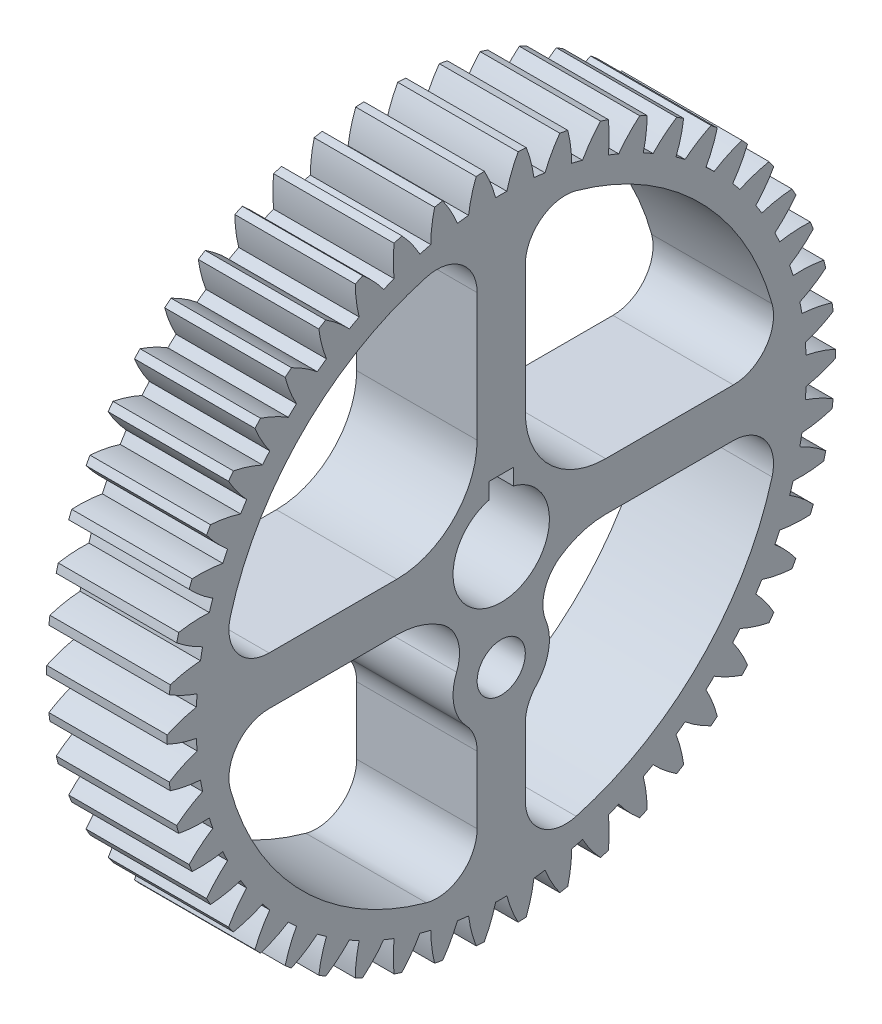
SolidWorks part; units mm, degrees
ref_plane "Plane1" through (0, 0, 0) normal (0, 0, 1) x (1, 0, 0)
ref_plane "Plane2" through (0, 0, 0) normal (0, 1, 0) x (1, 0, 0)
ref_plane "Plane3" through (0, 0, 0) normal (1, 0, 0) x (0, 0, -1)
other "Configuration Table"
sketch "HoldingSke" plane through (0, 0, 0) normal (0, 1, 0) x (1, 0, 0)
  line L0 (0, 0) -> (0.8035, -0.9576)
  line L1 (-15, 0) -> (100, 0) construction
  line L2 (0, 0) -> (-2.1039, 2.3779)
  line L3 (0, 0) -> (-11.863, 4.5341)
  line L4 (0, 0) -> (5.5511, 6.6156)
  line L5 (0, 0) -> (-46.8476, -17.4728)
  line L6 (0, 0) -> (-6.2172, -4.1948)
  line L7 (-2.1039, 2.3779) -> (8.6586, 51.2059)
  line L8 (-76.2, 54.61) -> (-76.1, 54.61)
  line L9 (-71.009, 38.7566) -> (-53.1078, 45.2721)
  line L10 (-76.2, 71.12) -> (104.1128, 71.12)
  line L11 (0, 0) -> (-7.5, 0)
  line L12 (-76.2, 101.6) -> (-76.17, 101.6)
  line L13 (24.9733, 27.94) -> (52.9518, 28.4284)
  line L14 (24.9733, 27.94) -> (24.9743, 27.94)
  line L15 (24.9733, 27.94) -> (100.4006, 29.5858)
  line L16 (-63.627, -0.8) -> (-12.827, -0.8)
  circle A0 centre (0, 0) radius 0.4
  circle A1 centre (0, 0) radius 18.999
  circle A2 centre (0, 0) radius 37.5
  circle A3 centre (0, 0) radius 0.4
  dimension "MHD" = 37.998
  dimension "Hub_dia" = 75
  dimension "Bore" = 0.8
  dimension "MBD" = 0.8
  dimension "Num_teeth" = 50
  dimension "Pitch" = 1.25
  dimension "Overall_len" = 50
  dimension "Show_teeth" = 50
  dimension "Thickness" = 7.5
  dimension "OAL" = 50.0001
  dimension "T_dim" = 0.1
  dimension "Ap" = 20
  dimension "H" = 19.05
  dimension "Pitch_radius" = 180.3128
  dimension "Width" = 7.5
  dimension "Backlash" = 0.03
  dimension "Addendum_fac" = 1
  dimension "Dedendum_fac" = 1.25
  dimension "Clearance_fac" = 0.25
  dimension "Dedendum_add" = 0.001
  dimension "Module" = 0.8
sketch "BasProSke" plane through (0, 0, 0) normal (0, 1, 0) x (1, 0, 0)
  line L0 (-10, 0) -> (60, 0) construction
  line L1 (0, 0) -> (0, 20.8)
  line L2 (0, 0) -> (7.5, 0)
  line L3 (7.5, 0) -> (7.5, 20.8)
  line L4 (7.5, 20.8) -> (0, 20.8)
  dimension "Thickness" = 7.5
  dimension "Diameter" = 41.6
revolve "Base-Revolve" add sketch "BasProSke" angle 360 about L0
sketch "TooCutSke" plane through (0, 0, 0) normal (1, 0, 0) x (0, 0, -1)
  line L1 (0, 0) -> (0, 107) construction
  line L2 (0, 0) -> (-0.6807, 19.9884) construction
  line L3 (0, 0) -> (-2.5106, 39.9045) construction
  line L4 (-0.6807, 19.9884) -> (-1.2553, 19.9523) construction
  arc A0 (0.3494, 18.9958) -> (-0.3494, 18.9958) centre (0, 0) ccw
  arc A1 (1.0655, 20.7981) -> (-1.0655, 20.7981) centre (0, 0) ccw
  circle A2 centre (0, 0) radius 20 construction
  circle A3 centre (0, 0) radius 18.7939 construction
  arc A4 (-0.3494, 18.9958) -> (-1.0655, 20.7981) centre (-8.0873, 16.9648) ccw
  arc A5 (1.0655, 20.7981) -> (0.3494, 18.9958) centre (8.0873, 16.9648) ccw
  dimension "Root_dia" = 37.998
  dimension "Overcut_dia" = 41.6508
  dimension "Pitch_dia" = 40
  dimension "Base_dia" = 37.5877
  dimension "Flank_rad" = 8
  dimension "Half_ang" = 3.6
  dimension "Half_CT" = 0.5757
extrude "ToothCut" cut sketch "TooCutSke" along normal through all
fillet "Breaks" [suppressed] radius 0.016 tangent propagation no
fillet "RootFillets" [suppressed] radius 0.201
pattern_circular "TeethCuts" count 50 every 7.2 about axis through (-10, 0, 0) along (1, 0, 0) of "ToothCut", "RootFillets", "Breaks"
sketch "HubNeaOneSke" plane through (0, 0, 0) normal (-1, 0, 0) x (0, 0, 1)
  circle A0 centre (0, 0) radius 18.999
  dimension "Diameter" = 37.998
extrude "HubNearOne" [suppressed] add sketch "HubNeaOneSke" along normal blind 42.5001
sketch "HubNeaBotSke" plane through (0, 0, 0) normal (-1, 0, 0) x (0, 0, 1)
  circle A0 centre (0, 0) radius 18.999
  dimension "Diameter" = 37.998
extrude "HubNearBoth" [suppressed] add sketch "HubNeaBotSke" along normal blind 21.25
ref_plane "FarPln" through (7.5, 0, 0) normal (1, 0, 0) x (0, 0, -1)
sketch "HubFarSke" plane through (7.5, 0, 0) normal (1, 0, 0) x (0, 0, -1)
  circle A0 centre (0, 0) radius 18.999
  dimension "Diameter" = 37.998
extrude "HubFar" [suppressed] add sketch "HubFarSke" along normal blind 21.25
sketch "BorSke" plane through (0, 0, 0) normal (1, 0, 0) x (0, 0, -1)
  circle A0 centre (0, 0) radius 0.4
  dimension "Diameter" = 0.8
extrude "Bore" cut sketch "BorSke" along normal mid plane 100.0001
sketch "KeySke" plane through (0, 0, 0) normal (1, 0, 0) x (0, 0, -1)
  line L0 (-0.05, 0) -> (-0.05, 0.5)
  line L1 (-0.05, 0.5) -> (0.05, 0.5)
  line L2 (0.05, 0.5) -> (0.05, 0)
  line L3 (0, 0) -> (0, 34) construction
  line L4 (-0.05, 0) -> (0.05, 0)
  dimension "Offset" = 0.5
  dimension "Width" = 0.1
extrude "Keyway" [suppressed] cut sketch "KeySke" along normal mid plane 100.0001
pattern_circular "Keyway2" [suppressed] count 2 every 90 about axis through (-10, 0, 0) along (1, 0, 0)
sketch "Sketch1" plane through (7.5, 0, 0) normal (1, 0, 0) x (0, 0, -1)
  circle A0 centre (0, 0) radius 0.4 construction
  circle A1 centre (0, 0) radius 0.4
extrude "Boss-Extrude1" add sketch "Sketch1" against normal up to surface (7.5 mm away) up to face at (0, 0, -0.4)
sketch "Sketch2" plane through (7.5, 0, 0) normal (1, 0, 0) x (0, 0, -1)
  line L0 (-13.0057, 13.8497) -> (-11.9789, 12.7562) construction
  circle A0 centre (0, 0) radius 17.499
  arc A1 (-12.7488, 14.0865) -> (-13.2582, 13.6081) centre (0, 0) ccw construction
  dimension "D1" = 1.5
extrude "Cut-Extrude1" cut sketch "Sketch2" against normal through all
sketch "Sketch3" plane through (7.5, 0, 0) normal (1, 0, 0) x (0, 0, -1)
  line L0 (17.499, 0) -> (-17.499, 0) construction
  line L1 (0, -17.499) -> (0, 17.499) construction
  line L2 (1.5, -17.4346) -> (1.5, -6.5)
  line L3 (-1.5, -17.4346) -> (-1.5, -6.5)
  line L4 (17.4346, 1.5) -> (6.5, 1.5)
  line L5 (17.4346, -1.5) -> (6.5, -1.5)
  line L6 (-1.5, 6.5) -> (-1.5, 17.4346)
  line L7 (-1.5, -17.499) -> (-1.5, 17.499) construction
  line L8 (-6.5, 1.5) -> (-17.4346, 1.5)
  line L9 (17.499, 1.5) -> (-17.499, 1.5) construction
  line L10 (1.5, 6.5) -> (1.5, 17.4346)
  line L11 (1.5, -17.499) -> (1.5, 17.499) construction
  line L12 (-6.5, -1.5) -> (-17.4346, -1.5)
  line L13 (17.499, -1.5) -> (-17.499, -1.5) construction
  circle A0 centre (0, 0) radius 17.499 construction
  arc A1 (-17.4346, 1.5) -> (-17.4346, -1.5) centre (0, 0) ccw
  arc A2 (-1.5, -17.4346) -> (1.5, -17.4346) centre (0, 0) ccw
  arc A3 (17.4346, -1.5) -> (17.4346, 1.5) centre (0, 0) ccw
  arc A4 (1.5, 17.4346) -> (-1.5, 17.4346) centre (0, 0) ccw
  arc A5 (-6.5, -1.5) -> (-1.5, -6.5) centre (-6.5, -6.5) cw
  arc A6 (1.5, -6.5) -> (6.5, -1.5) centre (6.5, -6.5) cw
  arc A7 (6.5, 1.5) -> (1.5, 6.5) centre (6.5, 6.5) cw
  arc A8 (-1.5, 6.5) -> (-6.5, 1.5) centre (-6.5, 6.5) cw
  point P6 (0, 0)
  point P9 (0, 0)
  point P34 (1.5, 1.5)
  point P37 (-1.5, 1.5)
  dimension "D5" = 5
  dimension "D1" = 1.5
  dimension "D2" = 1.5
  dimension "D3" = 1.5
  dimension "D4" = 1.5
extrude "Boss-Extrude2" add sketch "Sketch3" against normal up to surface (7.5 mm away) up to face at (0, 0, -17.499)
fillet "Fillet1" radius 2.5 8 edges at (3.75, -17.4346, 1.5) (3.75, -17.4346, -1.5) (3.75, -1.5, -17.4346) (3.75, 1.5, -17.4346) (3.75, 17.4346, -1.5) (3.75, -1.5, 17.4346) (3.75, 17.4346, 1.5) (3.75, 1.5, 17.4346)
sketch "Sketch4" plane through (7.5, 0, 0) normal (1, 0, 0) x (0, 0, -1)
  line L0 (0, 0) -> (0, 50000) construction
  line L1 (-0.75, 2.9047) -> (-0.75, 3.9047)
  line L2 (0.75, 2.9047) -> (0.75, 3.9047)
  line L3 (-0.75, 3.9047) -> (0.75, 3.9047)
  arc A0 (-0.75, 2.9047) -> (0.75, 2.9047) centre (0, 0) ccw
  dimension "D1" = 6
  dimension "D2" = 1
  dimension "D3" = 1.5
extrude "Cut-Extrude2" cut sketch "Sketch4" against normal through all
sketch "Sketch5" plane through (7.5, 0, 0) normal (1, 0, 0) x (0, 0, -1)
  line L0 (0, -6.5) -> (0, 0) construction
  circle A0 centre (0, -6.5) radius 3
  dimension "D2" = 6
  dimension "D1" = 6.5
extrude "Boss-Extrude3" add sketch "Sketch5" against normal up to surface (7.5 mm away) up to face at (0, 1.9286, 0)
sketch "Sketch6" plane through (7.5, 0, 0) normal (1, 0, 0) x (0, 0, -1)
  arc A1 (1.5, -9.0981) -> (2.0192, -4.2813) centre (0, -6.5) ccw construction
  circle A2 centre (0, -6.5) radius 1.5
  arc A4 (1.5, -9.0981) -> (2.0192, -4.2813) centre (0, -6.5) ccw construction
  point P5 (0, 0)
  dimension "D1" = 3
extrude "Cut-Extrude3" cut sketch "Sketch6" against normal through all
fillet "Fillet2" radius 2.5 4 edges at (3.75, -9.0981, 1.5) (3.75, -9.0981, -1.5) (3.75, -4.2813, -2.0192) (3.75, -4.2813, 2.0192)
equation "' \"Module@HoldingSke\" = 6.35"
equation "' \"Num_teeth@HoldingSke\" = 12"
equation "' \"Ap@HoldingSke\" =  20"
equation "' \"Ap@HoldingSke\" = 20"
equation "' \"Width@HoldingSke\" = 0.5 * 25.4"
equation "' \"Hub_dia@HoldingSke\"= 1 * 25.4"
equation "' \"Hub_dia@HoldingSke\" = 1 * 25.4"
equation "' \"Overall_len@HoldingSke\" = 1.0 * 25.4"
equation "' \"Bore@HoldingSke\" = 0.75 * 25.4"
equation "' \"T_dim@HoldingSke\" = 0.1 * 25.4"
equation "' \"Width@KeySke\" = 0.25 * 25.4"
equation "' \"Show_teeth@HoldingSke\" = 13"
equation "' \"Backlash@HoldingSke\" = 0.009 * 25.4"
equation "' \"Addendum_fac@HoldingSke\" = 1.0"
equation "' \"Dedendum_fac@HoldingSke\" = 1.25"
equation "' \"Dedendum_add@HoldingSke\" = 0.00005 * 25.4"
equation "' \"Clearance_fac@HoldingSke\" = 0.25"
equation "\"Pitch@HoldingSke\" = 1 / \"Module@HoldingSke\""
equation "\"Overcut_dia@TooCutSke\" = (\"Num_teeth@HoldingSke\" + 2 * \"Addendum_fac@HoldingSke\") / \"Pitch@HoldingSke\" + 0.002 * 25.4"
equation "\"Pitch_dia@TooCutSke\" = \"Num_teeth@HoldingSke\" / \"Pitch@HoldingSke\""
equation "\"Base_dia@TooCutSke\" = \"Num_teeth@HoldingSke\" / \"Pitch@HoldingSke\" * cos((\"Ap@HoldingSke\"  * 3.14159265 / 180))"
equation "\"Root_dia@TooCutSke\" = (\"Num_teeth@HoldingSke\" + 2) / \"Pitch@HoldingSke\" - 2 * (\"Addendum_fac@HoldingSke\" + \"Dedendum_fac@HoldingSke\") / \"Pitch@HoldingSke\" - \"Dedendum_add@HoldingSke\" * 2"
equation "\"Half_ang@TooCutSke\" = 180 / \"Num_teeth@HoldingSke\""
equation "\"Half_CT@TooCutSke\" = \"Num_teeth@HoldingSke\" / \"Pitch@HoldingSke\" * sin((3.14159265 / 2 / \"Num_teeth@HoldingSke\")) / 2 - 7 * \"Backlash@HoldingSke\" / 4"
equation "\"Flank_rad@TooCutSke\" = \"Num_teeth@HoldingSke\" / \"Pitch@HoldingSke\" / 5"
equation "\"Radius@RootFillets\" = \"Clearance_fac@HoldingSke\" / \"Pitch@HoldingSke\" + \"Dedendum_add@HoldingSke\""
equation "\"Break_rad@Breaks\" = 0.02 / \"Pitch@HoldingSke\""
equation "\"Thickness@HoldingSke\" = \"Width@HoldingSke\""
equation "\"OAL@HoldingSke\" = \"Thickness@HoldingSke\""
equation "\"MHD@HoldingSke\" = (\"Num_teeth@HoldingSke\" + 2) / \"Pitch@HoldingSke\" - 2 * (\"Addendum_fac@HoldingSke\" + \"Dedendum_fac@HoldingSke\")  / \"Pitch@HoldingSke\" - \"Dedendum_add@HoldingSke\" * 2"
equation "\"MBD@HoldingSke\" = (\"Num_teeth@HoldingSke\" + 2) / \"Pitch@HoldingSke\" - 2 * (\"Addendum_fac@HoldingSke\" + \"Dedendum_fac@HoldingSke\")  / \"Pitch@HoldingSke\" - \"Dedendum_add@HoldingSke\" * 2 - 0.002 * 25.4"
equation "\"MHD@HoldingSke\" = ((sgn( \"MHD@HoldingSke\" - \"Hub_dia@HoldingSke\" )-1)*( \"MHD@HoldingSke\" - \"Hub_dia@HoldingSke\" ))/-2+ \"Hub_dia@HoldingSke\""
equation "\"MBD@HoldingSke\" = ((sgn( \"MBD@HoldingSke\" - \"Bore@HoldingSke\" )-1)*( \"MBD@HoldingSke\" - \"Bore@HoldingSke\" ))/-2+ \"Bore@HoldingSke\""
equation "\"OAL@HoldingSke\" = ((sgn( \"OAL@HoldingSke\" - \"Overall_len@HoldingSke\" )+1)*( \"OAL@HoldingSke\" - \"Overall_len@HoldingSke\" ))/2 + \"Overall_len@HoldingSke\" + 0.000002 * 25.4"
equation "\"Num_teeth@TeethCuts\" = int( \"Show_teeth@HoldingSke\" ) + 1"
equation "\"Num_teeth@TeethCuts\" = ((sgn( \"Num_teeth@TeethCuts\" - \"Num_teeth@HoldingSke\" )-1)*( \"Num_teeth@TeethCuts\" - \"Num_teeth@HoldingSke\" ))/-2+ \"Num_teeth@HoldingSke\""
equation "\"Num_teeth@TeethCuts\" = ((sgn( \"Num_teeth@TeethCuts\" - 2.0)+1)*( \"Num_teeth@TeethCuts\" - 2.0))/2 +2.0"
equation "\"Angle@TeethCuts\" = 360.0 / \"Num_teeth@HoldingSke\""
equation "\"Diameter@BasProSke\" = (\"Num_teeth@HoldingSke\" + 2 * \"Addendum_fac@HoldingSke\") / \"Pitch@HoldingSke\""
equation "\"Thickness@BasProSke\"  = \"Thickness@HoldingSke\""
equation "' \"Fillet_rad@BasProSke\" =  \"Thickness@HoldingSke\" * 0.05"
equation "' \"Fillet_rad@BasProSke\" = \"Thickness@HoldingSke\" * 0.05"
equation "\"MHD@HoldingSke\" = ((sgn( \"MHD@HoldingSke\" - \"Root_dia@TooCutSke\" )-1)*( \"MHD@HoldingSke\" - \"Root_dia@TooCutSke\" ))/-2+ \"Root_dia@TooCutSke\""
equation "\"Diameter@HubNeaOneSke\" = \"MHD@HoldingSke\""
equation "\"Length@HubNearOne\" = \"OAL@HoldingSke\" - \"Thickness@BasProSke\""
equation "\"Diameter@HubNeaBotSke\" = \"MHD@HoldingSke\""
equation "\"Length@HubNearBoth\" = ( \"OAL@HoldingSke\" - \"Thickness@BasProSke\" ) / 2.0"
equation "\"Thickness@FarPln\" = \"Thickness@BasProSke\""
equation "\"Diameter@HubFarSke\" = \"MHD@HoldingSke\""
equation "\"Length@HubFar\" = ( \"OAL@HoldingSke\" - \"Thickness@BasProSke\" ) / 2.0"
equation "\"Diameter@BorSke\" = \"MBD@HoldingSke\""
equation "\"D1@Bore\" = \"OAL@HoldingSke\" * 2.0"
equation "\"D1@Keyway\" = \"OAL@HoldingSke\" * 2.0"
equation "\"Offset@KeySke\" = \"T_dim@HoldingSke\" + \"MBD@HoldingSke\" / 2.0"
